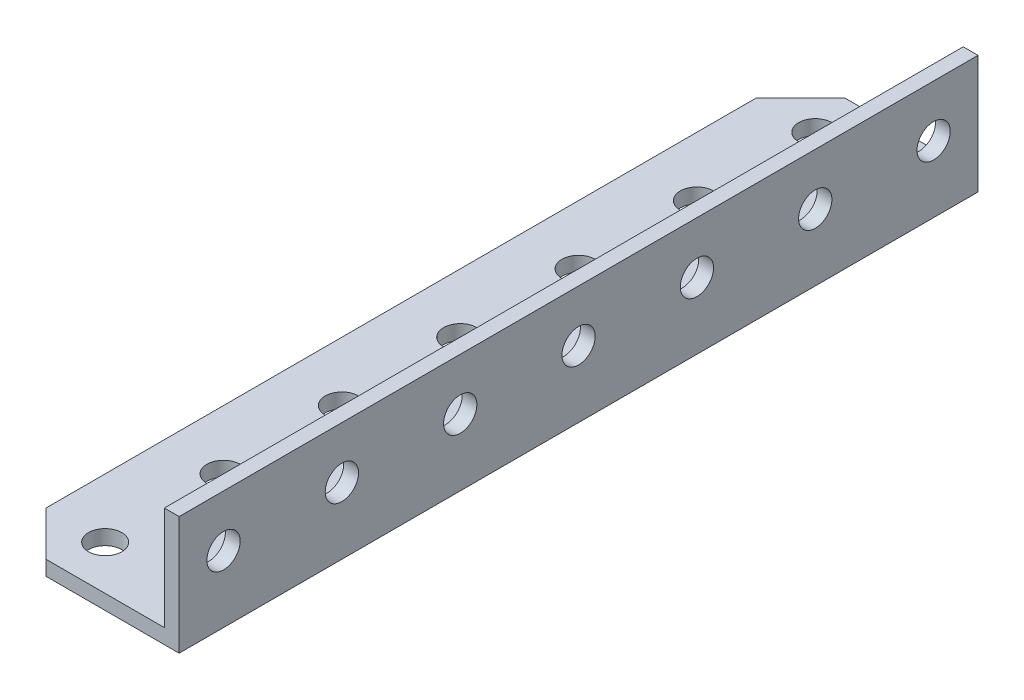
SolidWorks part; units mm, degrees
ref_plane "Front Plane" through (0, 0, 0) normal (0, 0, 1) x (1, 0, 0)
ref_plane "Top Plane" through (0, 0, 0) normal (0, 1, 0) x (1, 0, 0)
ref_plane "Right Plane" through (0, 0, 0) normal (1, 0, 0) x (0, 0, -1)
sketch "Sketch1" plane through (0, 0, 0) normal (0, 0, 1) x (1, 0, 0)
  line L0 (0, 0) -> (38.1, 0)
  line L1 (38.1, 0) -> (38.1, 25.4)
  line L2 (38.1, 25.4) -> (34.925, 25.4)
  line L3 (34.925, 25.4) -> (34.925, 3.175)
  line L4 (34.925, 3.175) -> (0, 3.175)
  line L5 (0, 3.175) -> (0, 0)
  dimension "D1" = 38.1
  dimension "D2" = 25.4
  dimension "D3" = 3.175
extrude "Boss-Extrude1" add sketch "Sketch1" along normal blind 177.8 contours L4 L5 L0 L1 L2 L3
sketch "Sketch6" plane through (0, 3.175, 0) normal (0, 1, 0) x (1, 0, 0)
  line L0 (12.7, -177.8) -> (12.7, 0) construction
  line L1 (34.925, -177.8) -> (0, -177.8) construction
  line L2 (34.925, 0) -> (0, 0) construction
  line L5 (34.925, -177.8) -> (34.925, 0) construction
  line L6 (12.7, -165.1) -> (12.7, -139.7) construction
  point P8 (12.7, -165.1)
  point P38 (12.7, -139.7)
  point P39 (12.7, -114.3)
  point P40 (12.7, -88.9)
  point P41 (12.7, -63.5)
  point P42 (12.7, -38.1)
  point P43 (12.7, -12.7)
  dimension "D1" = 22.225
  dimension "D2" = 12.7
  dimension "D4" = 25.4
  dimension "D3" = 7
hole_wizard "1/4 Clearance Hole1" positions "Sketch6" profile "Sketch7" hole size "1/4" standard "ANSI Inch" end condition up to next
sketch "Sketch7" plane through (12.7, 3.175, 12.7) normal (1, 0, 0) x (0, 0, 1)
  line L0 (0, 0) -> (0, 3.175)
  line L1 (0, 3.175) -> (3.5712, 3.175)
  line L2 (3.5712, 3.175) -> (3.5712, 0)
  line L5 (3.5712, 0) -> (0, 0)
  line L11 (0, -6.35) -> (0, 107.95) construction
  dimension "Thru Hole Dia." = 7.1425
  dimension "Thru Hole Depth" = 3.175
sketch "Sketch8" plane through (34.925, 0, 0) normal (-1, 0, 0) x (0, 0, 1)
  line L0 (0, 14.2875) -> (177.8, 14.2875) construction
  line L1 (0, 25.4) -> (0, 3.175) construction
  line L2 (177.8, 25.4) -> (177.8, 3.175) construction
  line L4 (12.7, 14.2875) -> (38.1, 14.2875) construction
  point P6 (12.7, 14.2875)
  point P26 (38.1, 14.2875)
  point P27 (63.5, 14.2875)
  point P28 (88.9, 14.2875)
  point P29 (114.3, 14.2875)
  point P30 (139.7, 14.2875)
  point P31 (165.1, 14.2875)
  point P32 (190.5, 14.2875)
  dimension "D1" = 12.7
  dimension "D3" = 25.4
  dimension "D2" = 8
hole_wizard "1/4 Clearance Hole2" positions "Sketch8" profile "Sketch9" hole size "1/4" standard "ANSI Inch" end condition up to next
sketch "Sketch9" plane through (34.925, 14.2875, 190.5) normal (0, 1, 0) x (0, 0, 1)
  line L0 (0, 0) -> (0, 3.175)
  line L1 (0, 3.175) -> (3.5712, 3.175)
  line L2 (3.5712, 3.175) -> (3.5712, 0)
  line L5 (3.5712, 0) -> (0, 0)
  line L11 (0, -6.35) -> (0, 107.95) construction
  dimension "Thru Hole Dia." = 7.1425
  dimension "Thru Hole Depth" = 3.175
chamfer "Chamfer1" distance 12.7 angle 45 2 edges at (0, 1.5875, 177.8) (0, 1.5875, 0)
ref_plane "Plane1" through (0, 0, 88.9) normal (0, 0, -1) x (-1, 0, 0)
sketch "Sketch10" plane through (0, 0, 0) normal (0, 0, -1) x (-1, 0, 0)
  line L1 (-38.1, 25.4) -> (0, 25.4)
  line L2 (-38.1, 25.4) -> (-38.1, 0)
  line L3 (-38.1, 0) -> (0, 0)
  line L4 (0, 25.4) -> (0, 0)
extrude "Cut-Extrude1" cut sketch "Sketch10" against normal blind 3.175
mirror "Mirror1" about plane through (0, 0, 88.9) normal (0, 0, -1) of "Cut-Extrude1"
